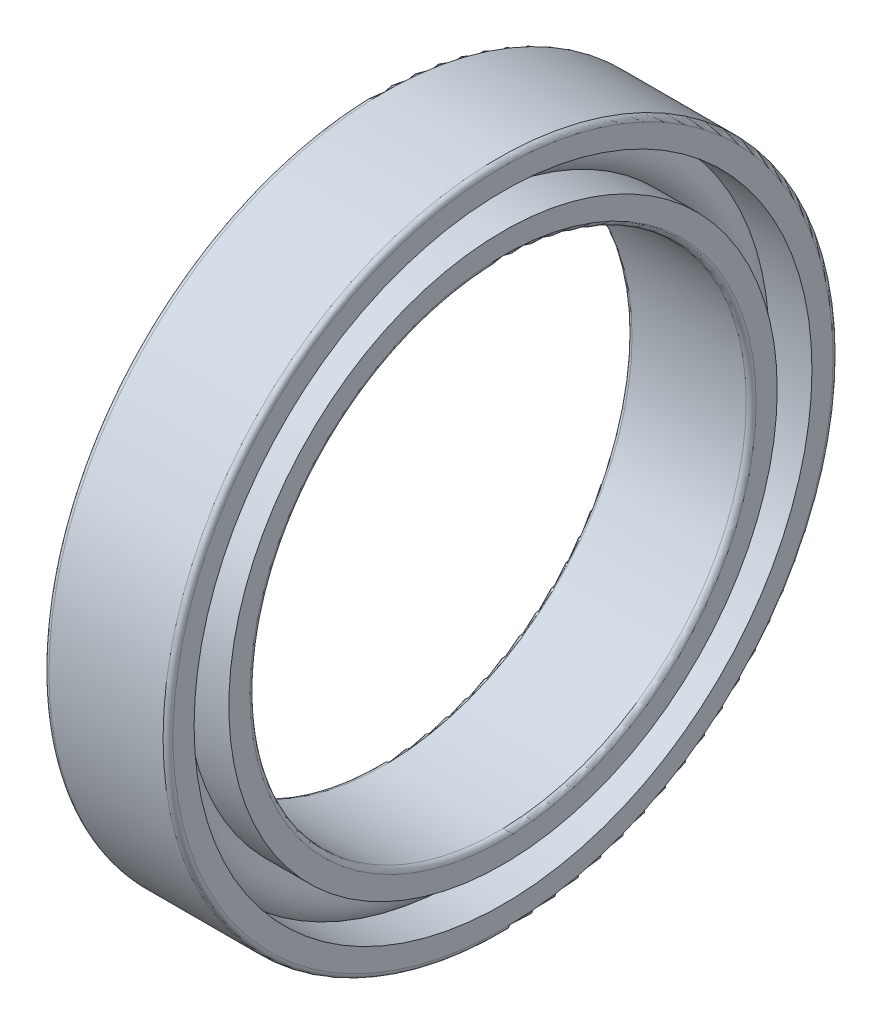
SolidWorks part; units mm, degrees
ref_plane "Plane1" through (0, 0, 0) normal (0, 0, 1) x (1, 0, 0)
ref_plane "Plane2" through (0, 0, 0) normal (0, 1, 0) x (1, 0, 0)
ref_plane "Plane3" through (0, 0, 0) normal (1, 0, 0) x (0, 0, -1)
sketch "Clipboard" plane through (0, 0, 0) normal (0, 0, 1) x (1, 0, 0)
  line L0 (-10, 0) -> (10, 0) construction
  line L1 (0, 0) -> (22.3471, -0.7804)
  line L2 (0, 0) -> (11.7428, 0.4101)
  line L3 (0, 0) -> (22.3471, -0.7804)
  line L4 (0, 0) -> (-22.3573, -0.3902)
  dimension "BallCLRad" = 11.75
sketch "CagSpiSke" plane through (0, 0, 0) normal (0, 0, 1) x (1, 0, 0)
  line L0 (0.105, 11.575) -> (0.105, 11.925)
  line L1 (0.105, 11.925) -> (-0.105, 11.925)
  line L2 (-0.105, 11.925) -> (-0.105, 11.575)
  line L3 (-0.105, 11.575) -> (0.105, 11.575)
  line L4 (-20.6375, 0) -> (20.6375, 0) construction
  line L5 (0, 0) -> (0, 23.7692) construction
  dimension "OD" = 23.85
  dimension "ID" = 23.15
revolve "CageSpine" add sketch "CagSpiSke" angle 0.001 about L4 reverse direction yes
ref_axis "Axis1" through (-50, 0, 0) along (1, 0, 0)
sketch "CagBalSke" plane through (0, 0, 0) normal (0, 0, 1) x (1, 0, 0)
  line L0 (-1.155, 11.75) -> (1.155, 11.75)
  line L1 (-1.905, 11.75) -> (1.905, 11.75) construction
  line L2 (-10, 0) -> (10, 0) construction
  line L3 (0, 0) -> (0, 24) construction
  arc A0 (1.155, 11.75) -> (-1.155, 11.75) centre (0, 11.75) cw
  dimension "BallCLRad" = 11.75
revolve "CageBall" [suppressed] add sketch "CagBalSke" angle 360 about L1 reverse direction yes
pattern_circular "CageBalls" [suppressed] count 2 every 180 about axis through (-50, 0, 0) along (1, 0, 0)
sketch "CagTrmODSke" plane through (0, 0, 0) normal (0, 0, 1) x (1, 0, 0)
  line L0 (1.156, 11.925) -> (1.156, 12.906)
  line L1 (1.156, 12.906) -> (-1.156, 12.906)
  line L2 (-1.156, 12.906) -> (-1.156, 11.925)
  line L3 (-1.156, 11.925) -> (1.156, 11.925)
  line L4 (-20.6375, 0) -> (20.6375, 0) construction
  line L5 (0, 0) -> (0, 25) construction
  dimension "Width" = 2.312
  dimension "ID" = 23.85
  dimension "OD" = 25.812
revolve "CageTrimOD" [suppressed] cut sketch "CagTrmODSke" angle 360 about L4 reverse direction yes
sketch "CagTrmIDSke" plane through (0, 0, 0) normal (0, 0, 1) x (1, 0, 0)
  line L0 (1.156, 10.596) -> (1.156, 11.575)
  line L1 (1.156, 11.575) -> (-1.156, 11.575)
  line L2 (-1.156, 11.575) -> (-1.156, 10.596)
  line L3 (-1.156, 10.596) -> (1.156, 10.596)
  line L4 (-20.6375, 0) -> (20.6375, 0) construction
  line L5 (0, 0) -> (0, 25) construction
  dimension "Width" = 2.312
  dimension "ID" = 21.192
  dimension "OD" = 23.15
revolve "CageTrimID" [suppressed] cut sketch "CagTrmIDSke" angle 360 about L4 reverse direction yes
sketch "BalSimSke" plane through (0, 0, 0) normal (0, 0, 1) x (1, 0, 0)
  line L0 (-10, 0) -> (10, 0) construction
  line L1 (-10, 11.75) -> (10, 11.75) construction
  line L2 (0, 0) -> (0, 23) construction
  circle A0 centre (0, 11.75) radius 1.05
  dimension "BallCLRad" = 11.75
  dimension "Ball_diameter" = 2.1
revolve "BallsSimplified" add sketch "BalSimSke" angle 360 about L0
sketch "BalDetSke" plane through (0, 0, 0) normal (0, 0, 1) x (1, 0, 0)
  line L0 (-1.05, 11.75) -> (1.05, 11.75)
  line L1 (-1.905, 11.75) -> (1.905, 11.75) construction
  line L2 (0, 0) -> (0, 25) construction
  arc A0 (1.05, 11.75) -> (-1.05, 11.75) centre (0, 11.75) cw
  dimension "BallCLRad" = 11.75
  dimension "Ball_diameter" = 2.1
revolve "BallDetailed" [suppressed] add sketch "BalDetSke" angle 360 about L1 reverse direction yes
sketch "InnRacSke" plane through (0, 0, 0) normal (0, 0, 1) x (1, 0, 0)
  line L0 (-0.7487, 11.05) -> (-2.5, 11.05)
  line L1 (-2.5, 11.05) -> (-2.5, 10.2)
  line L2 (-2.3, 10) -> (2.3, 10)
  line L3 (2.5, 10.2) -> (2.5, 11.05)
  line L4 (2.5, 11.05) -> (0.7487, 11.05)
  line L5 (-20.6375, 0) -> (20.6375, 0) construction
  line L6 (0, 0) -> (0, 30) construction
  arc A0 (-2.5, 10.2) -> (-2.3, 10) centre (-2.3, 10.2) ccw
  arc A1 (2.3, 10) -> (2.5, 10.2) centre (2.3, 10.2) ccw
  arc A2 (0.7487, 11.05) -> (-0.7487, 11.05) centre (0, 11.75) cw
  dimension "BallCLRad" = 11.75
  dimension "Fillet_radius" = 0.2
  dimension "Ball_diameter" = 2.05
  dimension "ID" = 20
  dimension "OD" = 22.1
  dimension "Width" = 5
revolve "InnerRace" add sketch "InnRacSke" angle 360 about L5 reverse direction yes
sketch "OutRacSke" plane through (0, 0, 0) normal (0, 0, 1) x (1, 0, 0)
  line L0 (-0.7487, 12.45) -> (-2.5, 12.45)
  line L1 (-2.5, 12.45) -> (-2.5, 13.3)
  line L2 (-2.3, 13.5) -> (2.3, 13.5)
  line L3 (2.5, 13.3) -> (2.5, 12.45)
  line L4 (2.5, 12.45) -> (0.7487, 12.45)
  line L5 (-20.6375, 0) -> (20.6375, 0) construction
  line L6 (0, 0) -> (0, 30) construction
  arc A0 (-2.5, 13.3) -> (-2.3, 13.5) centre (-2.3, 13.3) cw
  arc A1 (2.3, 13.5) -> (2.5, 13.3) centre (2.3, 13.3) cw
  arc A2 (0.7487, 12.45) -> (-0.7487, 12.45) centre (0, 11.75) ccw
  dimension "BallCLRad" = 11.75
  dimension "Fillet_radius" = 0.2
  dimension "Ball_diameter" = 2.05
  dimension "Width" = 5
revolve "OuterRace" add sketch "OutRacSke" angle 360 about L5 reverse direction yes
pattern_circular "BallsDetailed" [suppressed] count 2 every 180 about axis through (-50, 0, 0) along (1, 0, 0)
equation "\"BallCLRad@Clipboard\" = ( \"OD@OutRacSke\" + \"ID@InnRacSke\" ) / 4"
equation "\"BallCLRad@BalSimSke\" = \"BallCLRad@Clipboard\""
equation "\"BallCLRad@BalDetSke\" = \"BallCLRad@Clipboard\""
equation "\"BallCLRad@InnRacSke\" = \"BallCLRad@Clipboard\""
equation "\"BallCLRad@OutRacSke\" = \"BallCLRad@Clipboard\""
equation "\"Ball_diameter@InnRacSke\" = \"Ball_diameter@BalDetSke\" - 0.05"
equation "\"Ball_diameter@OutRacSke\" = \"Ball_diameter@BalDetSke\" - 0.05"
equation "\"Ball_diameter@BalSimSke\" = \"Ball_diameter@BalDetSke\""
equation "\"Width@OutRacSke\" = \"Width@InnRacSke\""
equation "\"Fillet_radius@OutRacSke\" = \"Fillet_radius@InnRacSke\""
equation "\"Max_count@Clipboard\" = int( 3.14159265 / atn(( \"Ball_diameter@BalDetSke\" / 2) / sqr( \"BallCLRad@Clipboard\"  *  \"BallCLRad@Clipboard\" - ( \"Ball_diameter@BalDetSke\" / 2) *  ( \"Ball_diameter@BalDetSke\" / 2))))"
equation "\"Max_count@Clipboard\" = ((sgn( \"Max_count@Clipboard\" - \"Count@Clipboard\" )-1)*( \"Max_count@Clipboard\" - \"Count@Clipboard\" ))/-2+ \"Count@Clipboard\""
equation "\"Count@BallsDetailed\" = int( \"Show_count@Clipboard\" ) "
equation "\"Count@BallsDetailed\" = ((sgn( \"Count@BallsDetailed\" - \"Max_count@Clipboard\" )-1)*( \"Count@BallsDetailed\" - \"Max_count@Clipboard\" ))/-2+ \"Max_count@Clipboard\""
equation "\"Count@BallsDetailed\" = ((sgn( \"Count@BallsDetailed\" - \"Min_count@Clipboard\" )+1)*( \"Count@BallsDetailed\" - \"Min_count@Clipboard\"))/2 +\"Min_count@Clipboard\""
equation "\"Angle@BallsDetailed\" = 360.0 / \"Max_count@Clipboard\""
equation "\"BallCLRad@CagBalSke\" = \"BallCLRad@Clipboard\""
equation "\"Count@CageBalls\" = \"Count@BallsDetailed\""
equation "\"Angle@CageBalls\" = \"Angle@BallsDetailed\""
equation "\"Angle@CageSpine\" =  \"Angle@CageBalls\" * ( \"Count@CageBalls\" -1 + int( \"Count@CageBalls\" / \"Max_count@Clipboard\" ) )  + 0.001 -  int( \"Count@CageBalls\" / \"Max_count@Clipboard\" ) * 0.001"
equation "\"Angle@CageSpine\" =  \"Angle@CageSpine\" * int( \"Min_count@Clipboard\" / 2) + int(1 / \"Min_count@Clipboard\")  * 0.001"
equation "\"CageWallOD@CagBalSke\" =  \"Ball_diameter@BalDetSke\" * 1.1"
equation "\"Thickness@CagSpiSke\" =  \"Ball_diameter@BalDetSke\" * 0.1"
equation "\"OD@CagTrmODSke\" = \"BallCLRad@Clipboard\" * 2 + \"CageWallOD@CagBalSke\" + 0.002"
equation "\"ID@CagTrmODSke\" = \"BallCLRad@Clipboard\" * 2 + \"Ball_diameter@BalDetSke\" / 6"
equation "\"OD@CagTrmIDSke\" = \"BallCLRad@Clipboard\" * 2 - \"Ball_diameter@BalDetSke\" / 6"
equation "\"ID@CagTrmIDSke\" = \"BallCLRad@Clipboard\" * 2 - \"CageWallOD@CagBalSke\" + 0.002"
equation "\"OD@CagSpiSke\" = \"ID@CagTrmODSke\""
equation "\"ID@CagSpiSke\" = \"OD@CagTrmIDSke\""
equation "\"Width@CagTrmODSke\" = \"CageWallOD@CagBalSke\" + 0.002"
equation "\"Width@CagTrmIDSke\" = \"CageWallOD@CagBalSke\" + 0.002"
